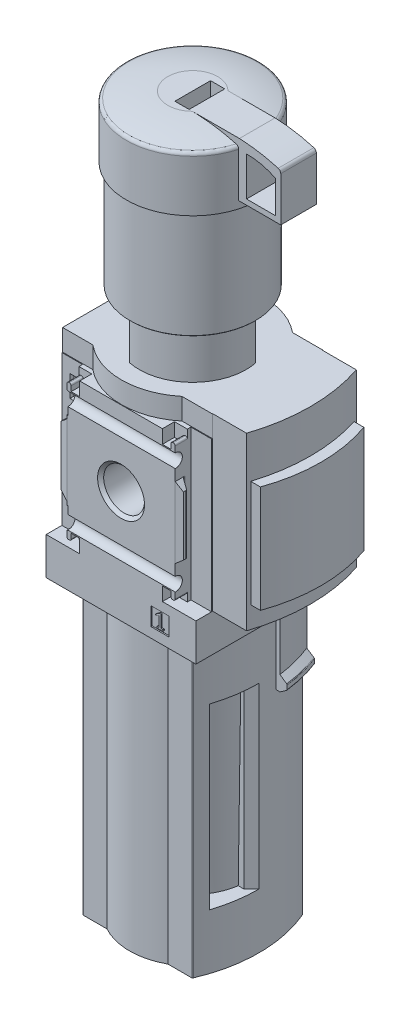
SolidWorks part; units mm, degrees
ref_plane "Front Plane" through (0, 0, 0) normal (0, 0, 1) x (1, 0, 0)
ref_plane "Top Plane" through (0, 0, 0) normal (0, 1, 0) x (1, 0, 0)
ref_plane "Right Plane" through (0, 0, 0) normal (1, 0, 0) x (0, 0, -1)
ref_plane "Plane1" through (0, 27, 0) normal (0, 1, 0) x (1, 0, 0)
sketch "Sketch1" plane through (0, 27, 0) normal (0, 1, 0) x (1, 0, 0)
  line L0 (-21, -15.5) -> (-12.5, -15.5)
  line L1 (12.5, -15.5) -> (21, -15.5)
  line L2 (21, -15.5) -> (21, 15.5)
  line L3 (21, 15.5) -> (12.5, 15.5)
  line L4 (-12.5, 15.5) -> (-21, 15.5)
  line L5 (-21, 15.5) -> (-21, -15.5)
  arc A0 (-12.5, -15.5) -> (12.5, -15.5) centre (0, -0.3889) ccw
  arc A1 (12.5, 15.5) -> (-12.5, 15.5) centre (0, 0.3889) ccw
extrude "Boss-Extrude1" add sketch "Sketch1" against normal blind 48
ref_plane "Plane2" through (0, 0, 0) normal (0, 0, 1) x (1, 0, 0)
sketch "Sketch2" plane through (0, 0, 0) normal (0, 0, 1) x (1, 0, 0)
  line L0 (-21, -21) -> (21, -21)
  line L1 (21, -21) -> (21, 21)
  line L2 (21, 21) -> (-21, 21)
  line L3 (-21, 21) -> (-21, -21)
extrude "Boss-Extrude2" add sketch "Sketch2" against normal blind 20.1 and the other way blind 20.1
ref_plane "Plane3" through (0, -31.5, 0) normal (0, 1, 0) x (1, 0, 0)
sketch "Sketch3" plane through (0, -31.5, 0) normal (0, 1, 0) x (1, 0, 0)
  line L0 (-21, -20.1) -> (21, -20.1)
  line L1 (21, -20.1) -> (21, 20.1)
  line L2 (21, 20.1) -> (-21, 20.1)
  line L3 (-21, 20.1) -> (-21, -20.1)
extrude "Boss-Extrude3" add sketch "Sketch3" along normal blind 10.5
ref_plane "Plane4" through (0, 0, -0.15) normal (0, 0, 1) x (1, 0, 0)
sketch "Sketch4" plane through (0, 0, -0.15) normal (0, 0, 1) x (1, 0, 0)
  line L0 (-15.3, -51.69) -> (19.65, -51.69)
  line L1 (19.65, -51.69) -> (21.5221, -50.3792)
  line L2 (21.65, -50.1334) -> (21.65, -49.0366)
  line L3 (21.5221, -48.7908) -> (19.65, -47.48)
  line L4 (19.65, -47.48) -> (19.65, -31.5)
  line L5 (19.65, -31.5) -> (-15.3, -31.5)
  line L6 (-15.3, -31.5) -> (-15.3, -51.69)
  line L7 (-20.3, -51.69) -> (-20.3, -31.5) construction
  arc A0 (21.5221, -50.3792) -> (21.65, -50.1334) centre (21.35, -50.1334) ccw
  arc A1 (21.65, -49.0366) -> (21.5221, -48.7908) centre (21.35, -49.0366) ccw
revolve "Revolve1" add sketch "Sketch4" angle 27 about L7
ref_plane "Plane5" through (0, -113.6, 0) normal (0, 1, 0) x (1, 0, 0)
sketch "Sketch5" plane through (0, -113.6, 0) normal (0, 1, 0) x (1, 0, 0)
  line L0 (-20, -20) -> (35, -20)
  line L1 (35, -20) -> (35, 20)
  line L2 (35, 20) -> (-20, 20)
  line L3 (-20, 20) -> (-20, -20)
  line L4 (-14.0907, -15.5) -> (-8.5463, -15.5)
  line L5 (8.5463, -15.5) -> (14.0907, -15.5)
  line L6 (17.2496, 5.142) -> (30, 5.142)
  line L7 (30, 5.142) -> (30, 15.349)
  line L8 (30, 15.349) -> (14.3511, 15.349)
  line L9 (14.0907, 15.5) -> (8.5463, 15.5)
  line L10 (-8.5463, 15.5) -> (-14.0907, 15.5)
  arc A0 (-14.3651, 15.3213) -> (-14.3651, -15.3213) centre (20.3, 0) ccw
  arc A1 (-14.3651, -15.3213) -> (-14.0907, -15.5) centre (-14.0907, -15.2) ccw
  arc A2 (-8.5463, -15.5) -> (8.5463, -15.5) centre (0, 0) ccw
  arc A3 (14.0907, -15.5) -> (14.3651, -15.3213) centre (14.0907, -15.2) ccw
  arc A4 (14.3651, -15.3213) -> (17.2496, 5.142) centre (-20.3, 0) ccw
  arc A5 (14.3511, 15.349) -> (14.0907, 15.5) centre (14.0907, 15.2) ccw
  arc A6 (8.5463, 15.5) -> (-8.5463, 15.5) centre (0, 0) ccw
  arc A7 (-14.0907, 15.5) -> (-14.3651, 15.3213) centre (-14.0907, 15.2) ccw
extrude "Cut-Extrude1" cut sketch "Sketch5" along normal blind 82.1
ref_plane "Plane6" through (0, -113.6, 0) normal (0, 1, 0) x (1, 0, 0)
sketch "Sketch6" plane through (0, -113.6, 0) normal (0, 1, 0) x (1, 0, 0)
  line L0 (-15.1813, -15.5) -> (-8.5463, -15.5)
  line L1 (8.5463, -15.5) -> (15.1813, -15.5)
  line L2 (15.1813, 15.5) -> (8.5463, 15.5)
  line L3 (-8.5463, 15.5) -> (-15.1813, 15.5)
  arc A0 (-15.457, 15.3181) -> (-15.457, -15.3181) centre (20.3, 0) ccw
  arc A1 (-15.457, -15.3181) -> (-15.1813, -15.5) centre (-15.1813, -15.2) ccw
  arc A2 (-8.5463, -15.5) -> (8.5463, -15.5) centre (0, 0) ccw
  arc A3 (15.1813, -15.5) -> (15.457, -15.3181) centre (15.1813, -15.2) ccw
  arc A4 (15.457, -15.3181) -> (15.457, 15.3181) centre (-20.3, 0) ccw
  arc A5 (15.457, 15.3181) -> (15.1813, 15.5) centre (15.1813, 15.2) ccw
  arc A6 (8.5463, 15.5) -> (-8.5463, 15.5) centre (0, 0) ccw
  arc A7 (-15.1813, 15.5) -> (-15.457, 15.3181) centre (-15.1813, 15.2) ccw
extrude "Boss-Extrude4" add sketch "Sketch6" along normal blind 82.1
ref_plane "Plane7" through (0, 0, 0) normal (0, 0, 1) x (1, 0, 0)
sketch "Sketch7" plane through (0, 0, 0) normal (0, 0, 1) x (1, 0, 0)
  line L0 (-30, -112.89) -> (-30, -113.6)
  line L1 (-30, -113.6) -> (-9.9875, -113.6)
  line L2 (-15.5092, -112.89) -> (-30, -112.89)
  line L3 (0, -112.89) -> (0, -113.6) construction
  arc A0 (-9.9875, -113.6) -> (-15.5092, -112.89) centre (0, -14.1) cw
revolve "Cut-Revolve1" cut sketch "Sketch7" angle 360 about L3 reverse direction yes
ref_plane "Plane8" through (0, -97.39, 0) normal (0, 1, 0) x (1, 0, 0)
sketch "Sketch8" plane through (0, -97.39, 0) normal (0, 1, 0) x (1, 0, 0)
  line L0 (-22.0154, -17.3124) -> (-14.603, -9.9)
  line L1 (-14.603, -9.9) -> (14.603, -9.9)
  line L2 (14.603, -9.9) -> (22.0154, -17.3124)
  line L3 (22.0154, -17.3124) -> (22.0154, 3.4154)
  line L4 (22.0154, 3.4154) -> (16.5, -2.1)
  line L5 (16.5, -2.1) -> (-16.5, -2.1)
  line L6 (-16.5, -2.1) -> (-22.0154, 3.4154)
  line L7 (-22.0154, 3.4154) -> (-22.0154, -17.3124)
extrude "Cut-Extrude2" cut sketch "Sketch8" along normal blind 50
ref_plane "Plane9" through (0, 0, 0) normal (0, 0, 1) x (1, 0, 0)
sketch "Sketch9" plane through (0, 0, 0) normal (0, 0, 1) x (1, 0, 0)
  line L0 (0, -47.39) -> (15.733, -47.39)
  line L1 (15.733, -47.39) -> (15.0215, -97.39)
  line L2 (15.0215, -97.39) -> (0, -97.39)
  line L3 (0, -97.39) -> (0, -47.39)
  line L4 (0, -97.39) -> (0, -47.39) construction
revolve "Revolve2" add sketch "Sketch9" angle 360 about L4 reverse direction yes
ref_plane "Plane10" through (0, 0, 0) normal (0, 0, 1) x (1, 0, 0)
sketch "Sketch10" plane through (0, 0, 0) normal (0, 0, 1) x (1, 0, 0)
  line L0 (0, 87.2) -> (7, 87.2)
  line L1 (18.6, 84.4576) -> (18.6, 70)
  line L2 (18.6, 70) -> (17.6, 70)
  line L3 (17.6, 70) -> (17.6, 40.2)
  line L4 (17.6, 40.2) -> (17.4, 40)
  line L5 (17.4, 40) -> (15, 40)
  line L6 (15, 40) -> (15, 27)
  line L7 (15, 27) -> (0, 27)
  line L8 (0, 27) -> (0, 87.2)
  line L9 (0, 27) -> (0, 87.2) construction
  arc A0 (7, 87.2) -> (17.8814, 85.4172) centre (5.2199, 42.2352) cw
  arc A1 (17.8814, 85.4172) -> (18.6, 84.4576) centre (17.6, 84.4576) cw
revolve "Revolve3" add sketch "Sketch10" angle 360 about L9
cosmetic thread "Cosmetic Thread1" parameters "D1"=13, "D2"=28.16
ref_plane "Plane11" through (0, 27, 0) normal (0, 1, 0) x (1, 0, 0)
sketch "Sketch11" plane through (0, 27, 0) normal (0, 1, 0) x (1, 0, 0)
  line L0 (20.9, -15.4) -> (30.5, -15.4)
  line L1 (30.5, 15.4) -> (20.9, 15.4)
  line L2 (20.9, 15.4) -> (20.9, -15.4)
  arc A0 (30.5, -15.4) -> (30.5, 15.4) centre (-15.682, 0) ccw
extrude "Boss-Extrude5" add sketch "Sketch11" against normal blind 48
ref_plane "Plane12" through (0, 15, 0) normal (0, 1, 0) x (1, 0, 0)
sketch "Sketch12" plane through (0, 15, 0) normal (0, 1, 0) x (1, 0, 0)
  line L0 (26, 14.5) -> (26, -14.5)
  line L1 (26, -14.5) -> (33.5, -14.5)
  line L2 (33.5, 14.5) -> (26, 14.5)
  arc A0 (33.5, -14.5) -> (33.5, 14.5) centre (-7.3, 0) ccw
extrude "Boss-Extrude6" add sketch "Sketch12" against normal blind 30
ref_plane "Plane13" through (0, 0, 0) normal (1, 0, 0) x (0, 0, -1)
sketch "Sketch13" plane through (0, 0, 0) normal (1, 0, 0) x (0, 0, -1)
  line L0 (-20.1, 0) -> (-20.1, 6.5785)
  line L1 (-20.1, 6.5785) -> (-19.244, 5.7225)
  line L2 (-19.244, 5.7225) -> (-7.799, 5.7225)
  line L3 (-7.799, 5.7225) -> (-6.943, 6.5785)
  line L4 (-6.943, 6.5785) -> (-6.943, 0)
  line L5 (-6.943, 0) -> (-20.1, 0)
  line L6 (-6.943, 0) -> (-20.1, 0) construction
revolve "Cut-Revolve2" cut sketch "Sketch13" angle 360 about L6 reverse direction yes
cosmetic thread "Cosmetic Thread2" parameters "D1"=13.157, "D2"=13.157
ref_plane "Plane14" through (0, 0, 0) normal (1, 0, 0) x (0, 0, -1)
sketch "Sketch14" plane through (0, 0, 0) normal (1, 0, 0) x (0, 0, -1)
  line L0 (6.943, 0) -> (6.943, 6.5785)
  line L1 (6.943, 6.5785) -> (7.799, 5.7225)
  line L2 (7.799, 5.7225) -> (19.244, 5.7225)
  line L3 (19.244, 5.7225) -> (20.1, 6.5785)
  line L4 (20.1, 6.5785) -> (20.1, 0)
  line L5 (20.1, 0) -> (6.943, 0)
  line L6 (20.1, 0) -> (6.943, 0) construction
revolve "Cut-Revolve3" cut sketch "Sketch14" angle 360 about L6 reverse direction yes
cosmetic thread "Cosmetic Thread3" parameters "D1"=13.157, "D2"=13.157
ref_plane "Plane15" through (0, 0, 20.1) normal (0, 0, 1) x (1, 0, 0)
sketch "Sketch15" plane through (0, 0, 20.1) normal (0, 0, 1) x (1, 0, 0)
  line L0 (8.4, -23.59) -> (8.4, -28.69)
  line L1 (8.4, -28.69) -> (13.5, -28.69)
  line L2 (13.5, -28.69) -> (13.5, -23.59)
  line L3 (13.5, -23.59) -> (8.4, -23.59)
  line L4 (9.6632, -25.02) -> (9.7613, -25.2755)
  line L5 (9.7613, -25.2755) -> (10.24, -25.0624)
  line L6 (10.24, -25.0624) -> (10.71, -24.78)
  line L7 (10.71, -24.78) -> (10.71, -27.76)
  line L8 (10.71, -27.76) -> (10.1, -27.76)
  line L9 (10.1, -27.76) -> (10.1, -28.14)
  line L10 (10.1, -28.14) -> (11.8, -28.14)
  line L11 (11.8, -28.14) -> (11.8, -27.76)
  line L12 (11.8, -27.76) -> (11.19, -27.76)
  line L13 (11.19, -27.76) -> (11.19, -24.21)
  line L14 (11.19, -24.21) -> (10.82, -24.21)
  line L15 (10.82, -24.21) -> (9.6632, -25.02)
extrude "Cut-Extrude3" cut sketch "Sketch15" against normal blind 0.35
ref_plane "Plane16" through (0, 0, -20.1) normal (0, 0, 1) x (1, 0, 0)
sketch "Sketch16" plane through (0, 0, -20.1) normal (0, 0, 1) x (1, 0, 0)
  line L0 (-13.5, -23.59) -> (-13.5, -28.69)
  line L1 (-13.5, -28.69) -> (-8.4, -28.69)
  line L2 (-8.4, -28.69) -> (-8.4, -23.59)
  line L3 (-8.4, -23.59) -> (-13.5, -23.59)
  line L4 (-12.0398, -25.2415) -> (-10.4706, -27.4826)
  line L5 (-10.5525, -27.64) -> (-12.15, -27.64)
  line L6 (-12.15, -27.64) -> (-12.15, -28.14)
  line L7 (-12.15, -28.14) -> (-9.75, -28.14)
  line L8 (-9.75, -28.14) -> (-9.75, -27.64)
  line L9 (-9.75, -27.64) -> (-11.5752, -25.0334)
  line L10 (-11.3704, -24.64) -> (-10.75, -24.64)
  line L11 (-10.25, -25.14) -> (-9.75, -25.14)
  line L12 (-10.75, -24.14) -> (-11.4664, -24.14)
  arc A0 (-11.4664, -24.14) -> (-12.0398, -25.2415) centre (-11.4664, -24.84) ccw
  arc A1 (-10.4706, -27.4826) -> (-10.5525, -27.64) centre (-10.5525, -27.54) cw
  arc A2 (-11.5752, -25.0334) -> (-11.3704, -24.64) centre (-11.3704, -24.89) cw
  arc A3 (-10.75, -24.64) -> (-10.25, -25.14) centre (-10.75, -25.14) cw
  arc A4 (-9.75, -25.14) -> (-10.75, -24.14) centre (-10.75, -25.14) ccw
extrude "Cut-Extrude4" cut sketch "Sketch16" along normal blind 0.35
ref_plane "Plane17" through (0, 0, 0) normal (1, 0, 0) x (0, 0, -1)
sketch "Sketch17" plane through (0, 0, 0) normal (1, 0, 0) x (0, 0, -1)
  line L0 (21.9, -15) -> (21.9, 15)
  line L1 (20.5, 13.167) -> (20.5, -13.167)
  arc A0 (20.5, -13.167) -> (21.9, -15) centre (20, -15) ccw
  arc A1 (21.9, 15) -> (20.5, 13.167) centre (20, 15) ccw
extrude "Cut-Extrude5" cut sketch "Sketch17" against normal blind 25 and the other way blind 25
ref_plane "Plane18" through (0, 0, 0) normal (1, 0, 0) x (0, 0, -1)
sketch "Sketch18" plane through (0, 0, 0) normal (1, 0, 0) x (0, 0, -1)
  line L0 (-21.9, 15) -> (-21.9, -15)
  line L1 (-20.5, -13.167) -> (-20.5, 13.167)
  arc A0 (-21.9, -15) -> (-20.5, -13.167) centre (-20, -15) ccw
  arc A1 (-20.5, 13.167) -> (-21.9, 15) centre (-20, 15) ccw
extrude "Cut-Extrude6" cut sketch "Sketch18" against normal blind 25 and the other way blind 25
ref_plane "Plane19" through (0, 0, 20.1) normal (0, 0, 1) x (1, 0, 0)
sketch "Sketch19" plane through (0, 0, 20.1) normal (0, 0, 1) x (1, 0, 0)
  line L0 (11.6, 21) -> (11.6, 17.2)
  line L1 (11.6, 17.2) -> (14, 17.2)
  line L2 (14, 17.2) -> (14, 18.6)
  line L3 (14.5, 19.1) -> (14.7, 19.1)
  line L4 (15.2, 18.6) -> (15.2, 9.95)
  line L5 (15.2, 9.95) -> (21.5, 4.6637)
  line L6 (21.5, 4.6637) -> (21.5, -4.6637)
  line L7 (21.5, -4.6637) -> (15.2, -9.95)
  line L8 (15.2, -9.95) -> (15.2, -18.6)
  line L9 (14.7, -19.1) -> (14.5, -19.1)
  line L10 (14, -18.6) -> (14, -17.2)
  line L11 (14, -17.2) -> (11.6, -17.2)
  line L12 (11.6, -17.2) -> (11.6, -21)
  line L13 (11.6, -21) -> (22, -21)
  line L14 (22, -21) -> (22, 21)
  line L15 (22, 21) -> (11.6, 21)
  arc A0 (14, 18.6) -> (14.5, 19.1) centre (14.5, 18.6) cw
  arc A1 (14.7, 19.1) -> (15.2, 18.6) centre (14.7, 18.6) cw
  arc A2 (15.2, -18.6) -> (14.7, -19.1) centre (14.7, -18.6) cw
  arc A3 (14.5, -19.1) -> (14, -18.6) centre (14.5, -18.6) cw
extrude "Cut-Extrude7" cut sketch "Sketch19" against normal blind 3.4 and the other way blind 3.4
ref_plane "Plane20" through (0, 0, 20.1) normal (0, 0, 1) x (1, 0, 0)
sketch "Sketch20" plane through (0, 0, 20.1) normal (0, 0, 1) x (1, 0, 0)
  line L0 (-22, -21) -> (-11.6, -21)
  line L1 (-11.6, -21) -> (-11.6, -17.2)
  line L2 (-11.6, -17.2) -> (-14, -17.2)
  line L3 (-14, -17.2) -> (-14, -18.6)
  line L4 (-14.5, -19.1) -> (-14.7, -19.1)
  line L5 (-15.2, -18.6) -> (-15.2, -9.95)
  line L6 (-15.2, -9.95) -> (-21.5, -4.6637)
  line L7 (-21.5, -4.6637) -> (-21.5, 4.6637)
  line L8 (-21.5, 4.6637) -> (-15.2, 9.95)
  line L9 (-15.2, 9.95) -> (-15.2, 18.6)
  line L10 (-14.7, 19.1) -> (-14.5, 19.1)
  line L11 (-14, 18.6) -> (-14, 17.2)
  line L12 (-14, 17.2) -> (-11.6, 17.2)
  line L13 (-11.6, 17.2) -> (-11.6, 21)
  line L14 (-11.6, 21) -> (-22, 21)
  line L15 (-22, 21) -> (-22, -21)
  arc A0 (-14, -18.6) -> (-14.5, -19.1) centre (-14.5, -18.6) cw
  arc A1 (-14.7, -19.1) -> (-15.2, -18.6) centre (-14.7, -18.6) cw
  arc A2 (-15.2, 18.6) -> (-14.7, 19.1) centre (-14.7, 18.6) cw
  arc A3 (-14.5, 19.1) -> (-14, 18.6) centre (-14.5, 18.6) cw
extrude "Cut-Extrude8" cut sketch "Sketch20" against normal blind 3.4 and the other way blind 3.4
ref_plane "Plane21" through (0, 0, -20.1) normal (0, 0, 1) x (1, 0, 0)
sketch "Sketch21" plane through (0, 0, -20.1) normal (0, 0, 1) x (1, 0, 0)
  line L0 (11.6, 21) -> (11.6, 17.2)
  line L1 (11.6, 17.2) -> (14, 17.2)
  line L2 (14, 17.2) -> (14, 18.6)
  line L3 (14.5, 19.1) -> (14.7, 19.1)
  line L4 (15.2, 18.6) -> (15.2, 9.95)
  line L5 (15.2, 9.95) -> (21.5, 4.6637)
  line L6 (21.5, 4.6637) -> (21.5, -4.6637)
  line L7 (21.5, -4.6637) -> (15.2, -9.95)
  line L8 (15.2, -9.95) -> (15.2, -18.6)
  line L9 (14.7, -19.1) -> (14.5, -19.1)
  line L10 (14, -18.6) -> (14, -17.2)
  line L11 (14, -17.2) -> (11.6, -17.2)
  line L12 (11.6, -17.2) -> (11.6, -21)
  line L13 (11.6, -21) -> (22, -21)
  line L14 (22, -21) -> (22, 21)
  line L15 (22, 21) -> (11.6, 21)
  arc A0 (14, 18.6) -> (14.5, 19.1) centre (14.5, 18.6) cw
  arc A1 (14.7, 19.1) -> (15.2, 18.6) centre (14.7, 18.6) cw
  arc A2 (15.2, -18.6) -> (14.7, -19.1) centre (14.7, -18.6) cw
  arc A3 (14.5, -19.1) -> (14, -18.6) centre (14.5, -18.6) cw
extrude "Cut-Extrude9" cut sketch "Sketch21" against normal blind 3.4 and the other way blind 3.4
ref_plane "Plane22" through (0, 0, -20.1) normal (0, 0, 1) x (1, 0, 0)
sketch "Sketch22" plane through (0, 0, -20.1) normal (0, 0, 1) x (1, 0, 0)
  line L0 (-22, -21) -> (-11.6, -21)
  line L1 (-11.6, -21) -> (-11.6, -17.2)
  line L2 (-11.6, -17.2) -> (-14, -17.2)
  line L3 (-14, -17.2) -> (-14, -18.6)
  line L4 (-14.5, -19.1) -> (-14.7, -19.1)
  line L5 (-15.2, -18.6) -> (-15.2, -9.95)
  line L6 (-15.2, -9.95) -> (-21.5, -4.6637)
  line L7 (-21.5, -4.6637) -> (-21.5, 4.6637)
  line L8 (-21.5, 4.6637) -> (-15.2, 9.95)
  line L9 (-15.2, 9.95) -> (-15.2, 18.6)
  line L10 (-14.7, 19.1) -> (-14.5, 19.1)
  line L11 (-14, 18.6) -> (-14, 17.2)
  line L12 (-14, 17.2) -> (-11.6, 17.2)
  line L13 (-11.6, 17.2) -> (-11.6, 21)
  line L14 (-11.6, 21) -> (-22, 21)
  line L15 (-22, 21) -> (-22, -21)
  arc A0 (-14, -18.6) -> (-14.5, -19.1) centre (-14.5, -18.6) cw
  arc A1 (-14.7, -19.1) -> (-15.2, -18.6) centre (-14.7, -18.6) cw
  arc A2 (-15.2, 18.6) -> (-14.7, 19.1) centre (-14.7, 18.6) cw
  arc A3 (-14.5, 19.1) -> (-14, 18.6) centre (-14.5, 18.6) cw
extrude "Cut-Extrude10" cut sketch "Sketch22" against normal blind 3.4 and the other way blind 3.4
ref_plane "Plane23" through (0, 0, 0) normal (0, 1, 0) x (1, 0, 0)
sketch "Sketch23" plane through (0, 0, 0) normal (0, 1, 0) x (1, 0, 0)
  line L0 (-22.2, 25.1) -> (-22.2, 15.7)
  line L1 (-22.2, 15.7) -> (-15.2, 15.7)
  line L2 (-15.2, 15.7) -> (-15.2, 17.4001)
  line L3 (-15.6493, 18.1191) -> (-16.9192, 18.7385)
  line L4 (-17.2, 19.1879) -> (-17.2, 19.8)
  line L5 (-17.2, 19.8) -> (-15.2, 20.1)
  line L6 (-15.2, 20.1) -> (15.2, 20.1)
  line L7 (15.2, 20.1) -> (17.2, 19.8)
  line L8 (17.2, 19.8) -> (17.2, 19.1879)
  line L9 (16.9192, 18.7385) -> (15.6493, 18.1191)
  line L10 (15.2, 17.4001) -> (15.2, 15.7)
  line L11 (15.2, 15.7) -> (22.2, 15.7)
  line L12 (22.2, 15.7) -> (22.2, 25.1)
  line L13 (22.2, 25.1) -> (-22.2, 25.1)
  arc A0 (-15.2, 17.4001) -> (-15.6493, 18.1191) centre (-16, 17.4001) ccw
  arc A1 (-16.9192, 18.7385) -> (-17.2, 19.1879) centre (-16.7, 19.1879) cw
  arc A2 (17.2, 19.1879) -> (16.9192, 18.7385) centre (16.7, 19.1879) cw
  arc A3 (15.6493, 18.1191) -> (15.2, 17.4001) centre (16, 17.4001) ccw
extrude "Cut-Extrude11" cut sketch "Sketch23" against normal blind 21 and the other way blind 21
ref_plane "Plane24" through (0, 0, 0) normal (0, 1, 0) x (1, 0, 0)
sketch "Sketch24" plane through (0, 0, 0) normal (0, 1, 0) x (1, 0, 0)
  line L0 (-22.2, -15.7) -> (-22.2, -25.1)
  line L1 (-22.2, -25.1) -> (22.2, -25.1)
  line L2 (22.2, -25.1) -> (22.2, -15.7)
  line L3 (22.2, -15.7) -> (15.2, -15.7)
  line L4 (15.2, -15.7) -> (15.2, -17.4001)
  line L5 (15.6493, -18.1191) -> (16.9192, -18.7385)
  line L6 (17.2, -19.1879) -> (17.2, -19.8)
  line L7 (17.2, -19.8) -> (15.2, -20.1)
  line L8 (15.2, -20.1) -> (-15.2, -20.1)
  line L9 (-15.2, -20.1) -> (-17.2, -19.8)
  line L10 (-17.2, -19.8) -> (-17.2, -19.1879)
  line L11 (-16.9192, -18.7385) -> (-15.6493, -18.1191)
  line L12 (-15.2, -17.4001) -> (-15.2, -15.7)
  line L13 (-15.2, -15.7) -> (-22.2, -15.7)
  arc A0 (15.2, -17.4001) -> (15.6493, -18.1191) centre (16, -17.4001) ccw
  arc A1 (16.9192, -18.7385) -> (17.2, -19.1879) centre (16.7, -19.1879) cw
  arc A2 (-17.2, -19.1879) -> (-16.9192, -18.7385) centre (-16.7, -19.1879) cw
  arc A3 (-15.6493, -18.1191) -> (-15.2, -17.4001) centre (-16, -17.4001) ccw
extrude "Cut-Extrude12" cut sketch "Sketch24" against normal blind 21 and the other way blind 21
ref_plane "Plane25" through (0, 87.2, 0) normal (0, 1, 0) x (1, 0, 0)
sketch "Sketch25" plane through (0, 87.2, 0) normal (0, 1, 0) x (1, 0, 0)
  line L0 (0, 5) -> (0, -5)
  line L1 (0, -5) -> (20, -5)
  line L2 (20, -5) -> (20, 5)
  line L3 (20, 5) -> (0, 5)
extrude "Cut-Extrude13" cut sketch "Sketch25" against normal blind 15
ref_plane "Plane26" through (0, 0, 0) normal (0, 0, 1) x (1, 0, 0)
sketch "Sketch26" plane through (0, 0, 0) normal (0, 0, 1) x (1, 0, 0)
  line L0 (4, 72) -> (29.7, 72)
  line L1 (29.7, 72) -> (29.7, 84.4576)
  line L2 (18.1, 87.2) -> (4, 87.2)
  line L3 (4, 87.2) -> (4, 72)
  line L4 (20.1, 84.4576) -> (20.1, 73.5)
  line L5 (20.1, 73.5) -> (28.2, 73.5)
  line L6 (28.2, 73.5) -> (28.2, 82.6)
  arc A0 (29.7, 84.4576) -> (28.9814, 85.4172) centre (28.7, 84.4576) ccw
  arc A1 (28.9814, 85.4172) -> (18.1, 87.2) centre (16.3199, 42.2352) ccw
  arc A2 (28.2, 82.6) -> (20.1, 84.4576) centre (20.235, 66.4581) ccw
extrude "Boss-Extrude7" add sketch "Sketch26" against normal blind 5 and the other way blind 5
ref_plane "Plane27" through (0, 27, 0) normal (0, 1, 0) x (1, 0, 0)
sketch "Sketch27" plane through (0, 27, 0) normal (0, 1, 0) x (1, 0, 0)
  line L0 (-49.4975, 7.0711) -> (7.0711, -49.4975)
  line L1 (7.0711, -49.4975) -> (49.4975, -7.0711)
  line L2 (49.4975, -7.0711) -> (-7.0711, 49.4975)
  line L3 (-7.0711, 49.4975) -> (-49.4975, 7.0711)
  line L4 (-30.052, 12.3744) -> (12.3744, -30.052)
  line L5 (12.3744, -30.052) -> (30.052, -12.3744)
  line L6 (30.052, -12.3744) -> (-12.3744, 30.052)
  line L7 (-12.3744, 30.052) -> (-30.052, 12.3744)
extrude "Cut-Extrude14" cut sketch "Sketch27" along normal blind 13
ref_plane "Plane28" through (0, 0, 0) normal (0, 0, 1) x (1, 0, 0)
sketch "Sketch28" plane through (0, 0, 0) normal (0, 0, 1) x (1, 0, 0)
  line L0 (-18.73, 10.97) -> (-14.92, 10.97)
  line L1 (-14.92, 10.97) -> (-14.92, 17.04)
  line L2 (-14.92, 17.04) -> (-18.73, 17.04)
  line L3 (-18.73, 17.04) -> (-18.73, 10.97)
extrude "Cut-Extrude15" cut sketch "Sketch28" against normal blind 22 and the other way blind 22
ref_plane "Plane29" through (0, 0, 0) normal (0, 0, 1) x (1, 0, 0)
sketch "Sketch29" plane through (0, 0, 0) normal (0, 0, 1) x (1, 0, 0)
  line L0 (-18.73, -17.03) -> (-14.92, -17.03)
  line L1 (-14.92, -17.03) -> (-14.92, -10.96)
  line L2 (-14.92, -10.96) -> (-18.73, -10.96)
  line L3 (-18.73, -10.96) -> (-18.73, -17.03)
extrude "Cut-Extrude16" cut sketch "Sketch29" against normal blind 22 and the other way blind 22
ref_plane "Plane30" through (-21, 0, 0) normal (1, 0, 0) x (0, 0, -1)
sketch "Sketch30" plane through (-21, 0, 0) normal (1, 0, 0) x (0, 0, -1)
  line L0 (-14.5, -18.95) -> (14.5, -18.95)
  line L1 (14.5, -18.95) -> (14.5, 18.95)
  line L2 (14.5, 18.95) -> (-14.5, 18.95)
  line L3 (-14.5, 18.95) -> (-14.5, -18.95)
extrude "Cut-Extrude17" cut sketch "Sketch30" against normal blind 11 and the other way blind 11
ref_plane "Plane31" through (0, 0, 0) normal (0, 1, 0) x (1, 0, 0)
sketch "Sketch31" plane through (0, 0, 0) normal (0, 1, 0) x (1, 0, 0)
  line L0 (-11.4891, -14.5) -> (-10, -14.5)
  line L1 (-10, -14.5) -> (-10, 14.5)
  line L2 (-10, 14.5) -> (-11.4891, 14.5)
  arc A0 (-11.4891, 14.5) -> (-11.4891, -14.5) centre (0, 0) ccw
extrude "Boss-Extrude8" add sketch "Sketch31" against normal blind 19 and the other way blind 19
ref_plane "Plane32" through (-19.9, 0, 0) normal (1, 0, 0) x (0, 0, -1)
sketch "Sketch32" plane through (-19.9, 0, 0) normal (1, 0, 0) x (0, 0, -1)
  line L0 (8.8, -21.3) -> (14.6, -21.3)
  line L1 (14.6, -21.3) -> (14.6, -17.1)
  line L2 (14.6, -17.1) -> (13.1633, -17.1)
  line L3 (8.8, -17.5) -> (8.8, -21.3)
  arc A0 (13.1633, -17.1) -> (8.8, -17.5) centre (11, -17.5) ccw
extrude "Boss-Extrude9" add sketch "Sketch32" along normal blind 9
ref_plane "Plane33" through (-19.9, 0, 0) normal (1, 0, 0) x (0, 0, -1)
sketch "Sketch33" plane through (-19.9, 0, 0) normal (1, 0, 0) x (0, 0, -1)
  line L0 (-14.6, 17.1) -> (-13.1633, 17.1)
  line L1 (-8.8, 17.5) -> (-8.8, 21.3)
  line L2 (-8.8, 21.3) -> (-14.6, 21.3)
  line L3 (-14.6, 21.3) -> (-14.6, 17.1)
  arc A0 (-13.1633, 17.1) -> (-8.8, 17.5) centre (-11, 17.5) ccw
extrude "Boss-Extrude10" add sketch "Sketch33" along normal blind 9
ref_plane "Plane34" through (-18, 0, 0) normal (1, 0, 0) x (0, 0, -1)
sketch "Sketch34" plane through (-18, 0, 0) normal (1, 0, 0) x (0, 0, -1)
  circle A0 centre (8.6, 6) radius 3.05
extrude "Boss-Extrude11" add sketch "Sketch34" along normal blind 5
